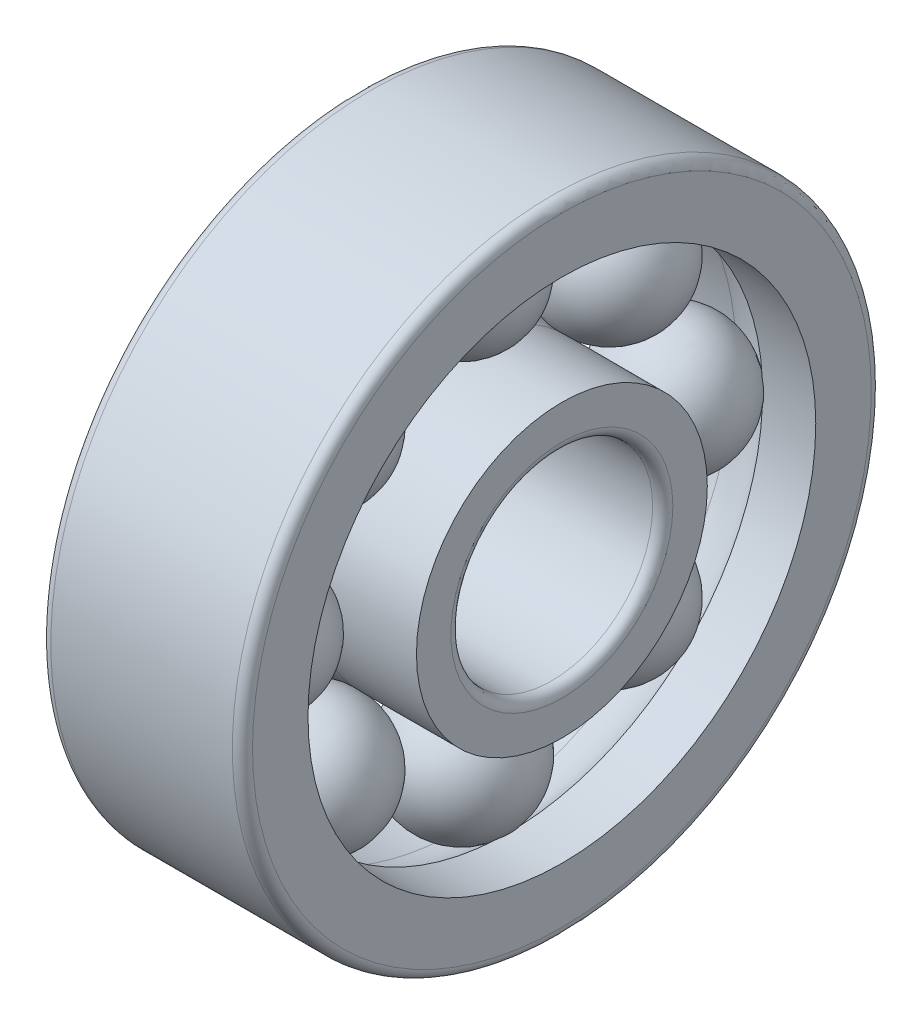
SolidWorks part; units mm, degrees
ref_plane "Plane1" through (0, 0, 0) normal (0, 0, 1) x (1, 0, 0)
ref_plane "Plane2" through (0, 0, 0) normal (0, 1, 0) x (1, 0, 0)
ref_plane "Plane3" through (0, 0, 0) normal (1, 0, 0) x (0, 0, -1)
sketch "Clipboard" plane through (0, 0, 0) normal (0, 0, 1) x (1, 0, 0)
  line L0 (-10, 0) -> (10, 0) construction
  line L1 (0, 0) -> (22.1431, -3.112)
  line L2 (0, 0) -> (6.1892, 0.8698)
  line L3 (0, 0) -> (22.1431, -3.112)
  line L4 (0, 0) -> (-22.3573, -0.3902)
  dimension "BallCLRad" = 6.25
sketch "CagSpiSke" plane through (0, 0, 0) normal (0, 0, 1) x (1, 0, 0)
  line L0 (0.4875, 5.925) -> (0.4875, 6.575)
  line L1 (0.4875, 6.575) -> (-0.4875, 6.575)
  line L2 (-0.4875, 6.575) -> (-0.4875, 5.925)
  line L3 (-0.4875, 5.925) -> (0.4875, 5.925)
  line L4 (-20.6375, 0) -> (20.6375, 0) construction
  line L5 (0, 0) -> (0, 23.7692) construction
  dimension "OD" = 13.15
  dimension "ID" = 11.85
revolve "CageSpine" add sketch "CagSpiSke" angle 0.001 about L4
ref_axis "Axis1" through (-50, 0, 0) along (1, 0, 0)
sketch "CagBalSke" plane through (0, 0, 0) normal (0, 0, 1) x (1, 0, 0)
  line L0 (-2.145, 6.25) -> (2.145, 6.25)
  line L1 (-1.905, 6.25) -> (1.905, 6.25) construction
  line L2 (-10, 0) -> (10, 0) construction
  line L3 (0, 0) -> (0, 24) construction
  arc A0 (2.145, 6.25) -> (-2.145, 6.25) centre (0, 6.25) cw
  dimension "BallCLRad" = 6.25
revolve "CageBall" [suppressed] add sketch "CagBalSke" angle 360 about L1 reverse direction yes
pattern_circular "CageBalls" [suppressed] count 8 every 45 about axis through (-50, 0, 0) along (1, 0, 0)
sketch "CagTrmODSke" plane through (0, 0, 0) normal (0, 0, 1) x (1, 0, 0)
  line L0 (2.146, 6.575) -> (2.146, 8.396)
  line L1 (2.146, 8.396) -> (-2.146, 8.396)
  line L2 (-2.146, 8.396) -> (-2.146, 6.575)
  line L3 (-2.146, 6.575) -> (2.146, 6.575)
  line L4 (-20.6375, 0) -> (20.6375, 0) construction
  line L5 (0, 0) -> (0, 25) construction
  dimension "Width" = 4.292
  dimension "ID" = 13.15
  dimension "OD" = 16.792
revolve "CageTrimOD" [suppressed] cut sketch "CagTrmODSke" angle 360 about L4 reverse direction yes
sketch "CagTrmIDSke" plane through (0, 0, 0) normal (0, 0, 1) x (1, 0, 0)
  line L0 (2.146, 4.106) -> (2.146, 5.925)
  line L1 (2.146, 5.925) -> (-2.146, 5.925)
  line L2 (-2.146, 5.925) -> (-2.146, 4.106)
  line L3 (-2.146, 4.106) -> (2.146, 4.106)
  line L4 (-20.6375, 0) -> (20.6375, 0) construction
  line L5 (0, 0) -> (0, 25) construction
  dimension "Width" = 4.292
  dimension "ID" = 8.212
  dimension "OD" = 11.85
revolve "CageTrimID" [suppressed] cut sketch "CagTrmIDSke" angle 360 about L4 reverse direction yes
sketch "BalSimSke" plane through (0, 0, 0) normal (0, 0, 1) x (1, 0, 0)
  line L0 (-10, 0) -> (10, 0) construction
  line L1 (-10, 6.25) -> (10, 6.25) construction
  line L2 (0, 0) -> (0, 23) construction
  circle A0 centre (0, 6.25) radius 1.95
  dimension "BallCLRad" = 6.25
  dimension "Ball_diameter" = 3.9
revolve "BallsSimplified" [suppressed] add sketch "BalSimSke" angle 360 about L0
sketch "BalDetSke" plane through (0, 0, 0) normal (0, 0, 1) x (1, 0, 0)
  line L0 (-1.95, 6.25) -> (1.95, 6.25)
  line L1 (-1.905, 6.25) -> (1.905, 6.25) construction
  line L2 (0, 0) -> (0, 25) construction
  arc A0 (1.95, 6.25) -> (-1.95, 6.25) centre (0, 6.25) cw
  dimension "BallCLRad" = 6.25
  dimension "Ball_diameter" = 3.9
revolve "BallDetailed" add sketch "BalDetSke" angle 360 about L1 reverse direction yes
sketch "InnRacSke" plane through (0, 0, 0) normal (0, 0, 1) x (1, 0, 0)
  line L0 (-1.4197, 4.95) -> (-3, 4.95)
  line L1 (-3, 4.95) -> (-3, 3.3)
  line L2 (-2.7, 3) -> (2.7, 3)
  line L3 (3, 3.3) -> (3, 4.325)
  line L4 (0, 4.325) -> (3, 4.325)
  line L5 (-20.6375, 0) -> (20.6375, 0) construction
  line L6 (0, 0) -> (0, 30) construction
  arc A0 (-3, 3.3) -> (-2.7, 3) centre (-2.7, 3.3) ccw
  arc A1 (2.7, 3) -> (3, 3.3) centre (2.7, 3.3) ccw
  arc A2 (0, 4.325) -> (-1.4197, 4.95) centre (0, 6.25) cw
  dimension "BallCLRad" = 6.25
  dimension "Fillet_radius" = 0.3
  dimension "Ball_diameter" = 3.85
  dimension "ID" = 6
  dimension "OD" = 9.9
  dimension "Width" = 6
revolve "InnerRace" add sketch "InnRacSke" angle 360 about L5 reverse direction yes
sketch "OutRacSke" plane through (0, 0, 0) normal (0, 0, 1) x (1, 0, 0)
  line L0 (0, 8.175) -> (-3, 8.175)
  line L1 (-3, 8.175) -> (-3, 9.2)
  line L2 (-2.7, 9.5) -> (2.7, 9.5)
  line L3 (3, 9.2) -> (3, 7.55)
  line L4 (3, 7.55) -> (1.4197, 7.55)
  line L5 (-20.6375, 0) -> (20.6375, 0) construction
  line L6 (0, 0) -> (0, 30) construction
  arc A0 (-3, 9.2) -> (-2.7, 9.5) centre (-2.7, 9.2) cw
  arc A1 (2.7, 9.5) -> (3, 9.2) centre (2.7, 9.2) cw
  arc A2 (1.4197, 7.55) -> (0, 8.175) centre (0, 6.25) ccw
  dimension "BallCLRad" = 6.25
  dimension "Fillet_radius" = 0.3
  dimension "Ball_diameter" = 3.85
  dimension "Width" = 6
revolve "OuterRace" add sketch "OutRacSke" angle 360 about L5 reverse direction yes
pattern_circular "BallsDetailed" count 8 every 45 about axis through (-50, 0, 0) along (1, 0, 0) of "BallDetailed"
equation "\"BallCLRad@Clipboard\" = ( \"OD@OutRacSke\" + \"ID@InnRacSke\" ) / 4"
equation "\"BallCLRad@BalSimSke\" = \"BallCLRad@Clipboard\""
equation "\"BallCLRad@BalDetSke\" = \"BallCLRad@Clipboard\""
equation "\"BallCLRad@InnRacSke\" = \"BallCLRad@Clipboard\""
equation "\"BallCLRad@OutRacSke\" = \"BallCLRad@Clipboard\""
equation "\"Ball_diameter@InnRacSke\" = \"Ball_diameter@BalDetSke\" - 0.05"
equation "\"Ball_diameter@OutRacSke\" = \"Ball_diameter@BalDetSke\" - 0.05"
equation "\"Ball_diameter@BalSimSke\" = \"Ball_diameter@BalDetSke\""
equation "\"Width@OutRacSke\" = \"Width@InnRacSke\""
equation "\"Fillet_radius@OutRacSke\" = \"Fillet_radius@InnRacSke\""
equation "\"Max_count@Clipboard\" = int( 3.14159265 / atn(( \"Ball_diameter@BalDetSke\" / 2) / sqr( \"BallCLRad@Clipboard\"  *  \"BallCLRad@Clipboard\" - ( \"Ball_diameter@BalDetSke\" / 2) *  ( \"Ball_diameter@BalDetSke\" / 2))))"
equation "\"Max_count@Clipboard\" = ((sgn( \"Max_count@Clipboard\" - \"Count@Clipboard\" )-1)*( \"Max_count@Clipboard\" - \"Count@Clipboard\" ))/-2+ \"Count@Clipboard\""
equation "\"Count@BallsDetailed\" = int( \"Show_count@Clipboard\" ) "
equation "\"Count@BallsDetailed\" = ((sgn( \"Count@BallsDetailed\" - \"Max_count@Clipboard\" )-1)*( \"Count@BallsDetailed\" - \"Max_count@Clipboard\" ))/-2+ \"Max_count@Clipboard\""
equation "\"Count@BallsDetailed\" = ((sgn( \"Count@BallsDetailed\" - \"Min_count@Clipboard\" )+1)*( \"Count@BallsDetailed\" - \"Min_count@Clipboard\"))/2 +\"Min_count@Clipboard\""
equation "\"Angle@BallsDetailed\" = 360.0 / \"Max_count@Clipboard\""
equation "\"BallCLRad@CagBalSke\" = \"BallCLRad@Clipboard\""
equation "\"Count@CageBalls\" = \"Count@BallsDetailed\""
equation "\"Angle@CageBalls\" = \"Angle@BallsDetailed\""
equation "\"Angle@CageSpine\" =  \"Angle@CageBalls\" * ( \"Count@CageBalls\" -1 + int( \"Count@CageBalls\" / \"Max_count@Clipboard\" ) )  + 0.001 -  int( \"Count@CageBalls\" / \"Max_count@Clipboard\" ) * 0.001"
equation "\"Angle@CageSpine\" =  \"Angle@CageSpine\" * int( \"Min_count@Clipboard\" / 2) + int(1 / \"Min_count@Clipboard\")  * 0.001"
equation "\"CageWallOD@CagBalSke\" =  \"Ball_diameter@BalDetSke\" * 1.1"
equation "\"Thickness@CagSpiSke\" =  \"Ball_diameter@BalDetSke\" * 0.25"
equation "\"OD@CagTrmODSke\" = \"BallCLRad@Clipboard\" * 2 + \"CageWallOD@CagBalSke\" + 0.002"
equation "\"ID@CagTrmODSke\" = \"BallCLRad@Clipboard\" * 2 + \"Ball_diameter@BalDetSke\" / 6"
equation "\"OD@CagTrmIDSke\" = \"BallCLRad@Clipboard\" * 2 - \"Ball_diameter@BalDetSke\" / 6"
equation "\"ID@CagTrmIDSke\" = \"BallCLRad@Clipboard\" * 2 - \"CageWallOD@CagBalSke\" + 0.002"
equation "\"OD@CagSpiSke\" = \"ID@CagTrmODSke\""
equation "\"ID@CagSpiSke\" = \"OD@CagTrmIDSke\""
equation "\"Width@CagTrmODSke\" = \"CageWallOD@CagBalSke\" + 0.002"
equation "\"Width@CagTrmIDSke\" = \"CageWallOD@CagBalSke\" + 0.002"
